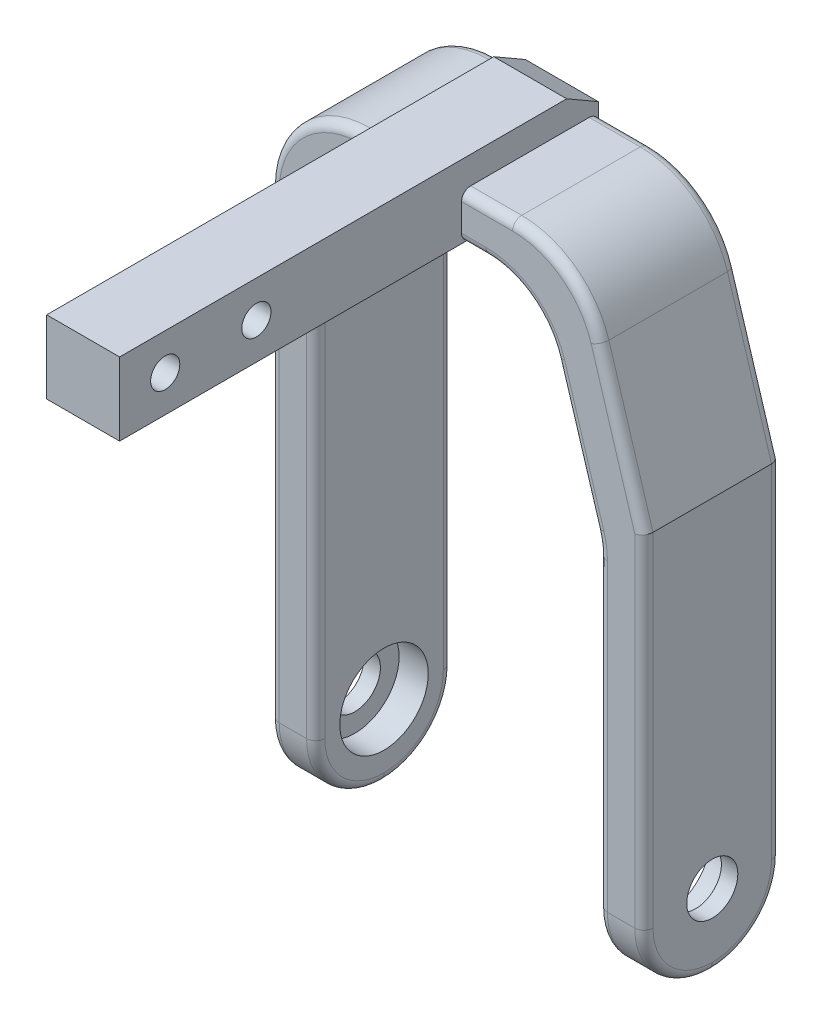
SolidWorks part; units mm, degrees
ref_plane "前视基准面" through (0, 0, 0) normal (0, 0, 1) x (1, 0, 0)
ref_plane "上视基准面" through (0, 0, 0) normal (0, 1, 0) x (1, 0, 0)
ref_plane "右视基准面" through (0, 0, 0) normal (1, 0, 0) x (0, 0, -1)
sketch "草图1" plane through (0, 0, 0) normal (0, 1, 0) x (1, 0, 0)
  line L1 (24, 7.5) -> (-17, 7.5)
  line L2 (24, 7.5) -> (24, -7.5)
  line L3 (24, -7.5) -> (-17, -7.5)
  line L4 (-17, 7.5) -> (-17, -7.5)
  line L5 (24, 7.5) -> (-17, -7.5) construction
  line L6 (24, -7.5) -> (-17, 7.5) construction
  point P0 (0, 0)
extrude "凸台-拉伸1" add sketch "草图1" against normal blind 68
sketch "草图3" plane through (0, 0, 7.5) normal (0, 0, 1) x (1, 0, 0)
  line L0 (-17, -68) -> (24, -68) construction
  line L1 (-12, -68) -> (19, -68)
  line L2 (-12, -68) -> (-12, -5)
  line L3 (-12, -5) -> (12.6087, -5)
  line L4 (19, -68) -> (19, -25.9143)
  line L5 (12.6087, -5) -> (19, -25.9143)
  line L6 (17, 0) -> (27.4891, -34.3238)
  line L7 (17, 0) -> (27.4891, 0)
  line L8 (27.4891, 0) -> (27.4891, -34.3238)
  line L9 (-17, 0) -> (24, 0) construction
  line L10 (-17, 0) -> (24, 0) construction
extrude "切除-拉伸1" cut sketch "草图3" against normal through all
fillet "圆角1" radius 8 3 edges at (-12, -5, 0) (19, -25.9143, 0) (12.6087, -5, 0)
fillet "圆角3" radius 7.5 4 edges at (21.5, -68, -7.5) (21.5, -68, 7.5) (-14.5, -68, -7.5) (-14.5, -68, 7.5)
sketch "草图4" plane through (24, 0, 0) normal (1, 0, 0) x (0, 0, -1)
  circle A0 centre (0, -60) radius 2.8
extrude "切除-拉伸2" cut sketch "草图4" against normal through all
sketch "草图6" plane through (19, 0, 0) normal (1, 0, 0) x (0, 0, -1)
  circle A0 centre (0, -60) radius 4.85
extrude "切除-拉伸4" cut sketch "草图6" along normal blind 3.2
ref_plane "基准面1" through (3.5, 0, 0) normal (1, 0, 0) x (0, 0, -1)
mirror "镜向2" about plane through (3.5, 0, 0) normal (1, 0, 0) of "切除-拉伸4"
sketch "草图7" plane through (0, 0, 0) normal (1, 0, 0) x (0, 0, -1)
  line L1 (-45, -5) -> (7.5, -5)
  line L2 (-45, -5) -> (-45, 3)
  line L3 (-45, 3) -> (7.5, 3)
  line L4 (7.5, -5) -> (7.5, 3)
  circle A2 centre (-30, -1) radius 1.6
  circle A3 centre (-40, -1) radius 1.6
extrude "凸台-拉伸2" add sketch "草图7" along normal mid plane 8
chamfer "倒角1" distance 2 angle 60 1 edges at (0, 3, -7.5) first distance on face at (4.7083, -20.0893, -7.5)
fillet "圆角4" radius 10 2 edges at (17, 0, 0) (-17, 0, 0)
fillet "圆角2" radius 1 36 edges at (-17, -35.25, -7.5) (24, -41.7031, -7.5) (24, -41.7031, 7.5) (-17, -35.25, 7.5) (-9.6569, -7.3431, 7.5) (5.3441, -5, 7.5) (19, -43.8047, 7.5) (19, -43.8047, -7.5) (1.3441, -5, -7.5) (-9.6569, -7.3431, -7.5) (-12, -36.75, -7.5) (-12, -36.75, 7.5) (19, -65.8033, 5.3033) (19, -65.8033, -5.3033) (-12, -65.8033, -5.3033) (-12, -65.8033, 5.3033) (-17, -65.8033, 5.3033) (-17, -65.8033, -5.3033) (24, -65.8033, -5.3033) (24, -65.8033, 5.3033) (11.4473, -6.5694, 7.5) (16.4949, -17.7167, 7.5) (18.9122, -25.9274, 7.5) (18.9122, -25.9274, -7.5) (16.4949, -17.7167, -7.5) (11.4473, -6.5694, -7.5) (21.5814, -14.9919, -7.5) (21.5814, -14.9919, 7.5) (6.7997, 0, -7.5) (15.5481, -1.9618, -7.5) (6.7997, 0, 7.5) (15.5481, -1.9618, 7.5) (-5.5, 0, -7.5) (-14.0711, -2.9289, -7.5) (-5.5, 0, 7.5) (-14.0711, -2.9289, 7.5)
